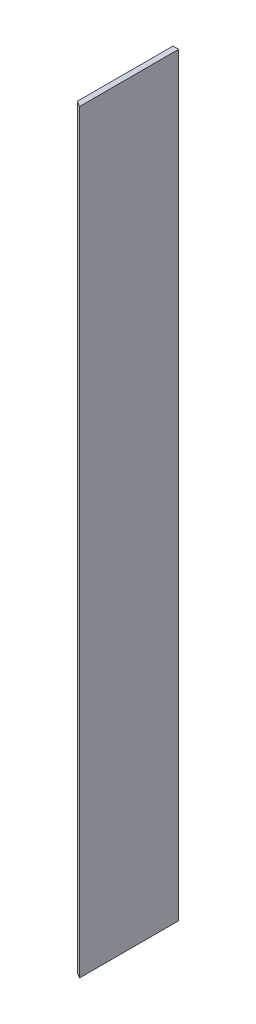
SolidWorks part; units mm, degrees
ref_plane "Спереди" through (0, 0, 0) normal (0, 0, 1) x (1, 0, 0)
ref_plane "Сверху" through (0, 0, 0) normal (0, 1, 0) x (1, 0, 0)
ref_plane "Справа" through (0, 0, 0) normal (1, 0, 0) x (0, 0, -1)
sketch "Эскиз1" plane through (0, 0, 0) normal (0, 1, 0) x (1, 0, 0)
  line L1 (1, 0) -> (5, 0)
  line L2 (1, 0) -> (1, -67.636)
  line L3 (1, -67.636) -> (5, -70.0688)
  line L4 (5, 0) -> (5, -70.0688)
  line L6 (5, -70.2138) -> (5, 227.4589) construction
  dimension "D1" = 4
extrude "Вытянуть1" add sketch "Эскиз1" along normal up to surface (533.2137 mm away)
